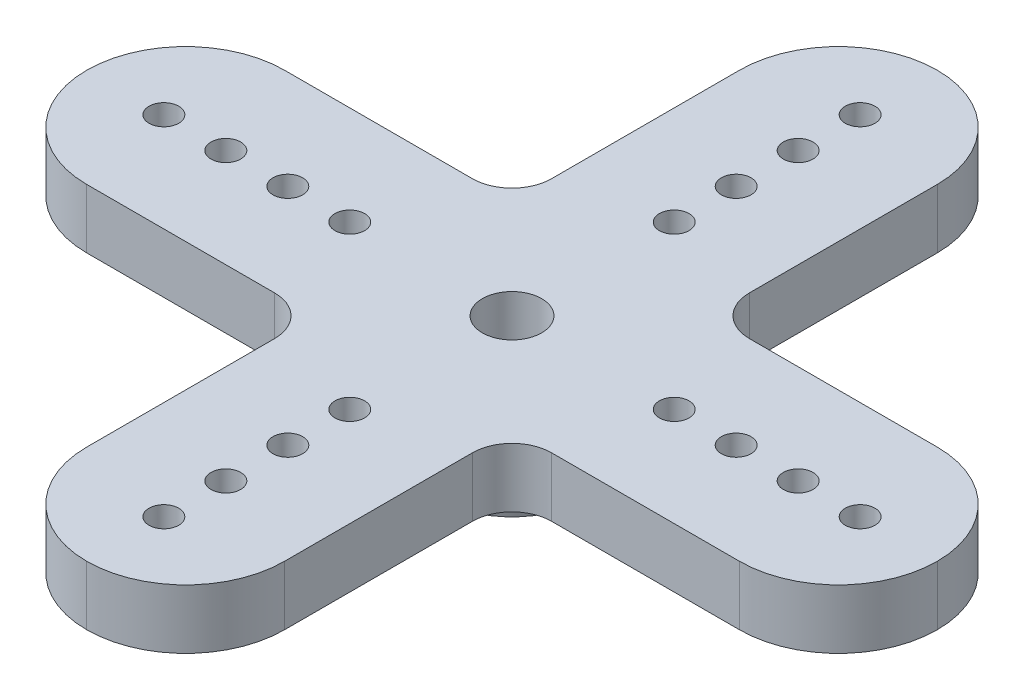
SolidWorks part; units mm, degrees
ref_plane "Front Plane" through (0, 0, 0) normal (0, 0, 1) x (1, 0, 0)
ref_plane "Top Plane" through (0, 0, 0) normal (0, 1, 0) x (1, 0, 0)
ref_plane "Right Plane" through (0, 0, 0) normal (1, 0, 0) x (0, 0, -1)
sketch "Sketch1" plane through (0, 0, 0) normal (0, 1, 0) x (1, 0, 0)
  line L0 (-5, 5) -> (-5, 21.5)
  line L1 (-5, 21.5) -> (5, 21.5)
  line L2 (5, 21.5) -> (5, 5)
  line L3 (5, 5) -> (21.5, 5)
  line L4 (21.5, 5) -> (21.5, -5)
  line L5 (21.5, -5) -> (5, -5)
  line L6 (5, -5) -> (5, -21.5)
  line L7 (5, -21.5) -> (-5, -21.5)
  line L8 (-5, -21.5) -> (-5, -5)
  line L9 (-5, -5) -> (-21.5, -5)
  line L10 (-21.5, -5) -> (-21.5, 5)
  line L11 (-21.5, 5) -> (-5, 5)
  point P2 (0, 21.5)
  point P13 (-21.5, 0)
  dimension "D1" = 10
  dimension "D2" = 43
extrude "Boss-Extrude1" add sketch "Sketch1" along normal blind 3
fillet "Fillet1" radius 2 4 edges at (-5, 1.5, -5) (5, 1.5, -5) (-5, 1.5, 5) (5, 1.5, 5)
fillet "Fillet2" radius 5 8 edges at (-21.5, 1.5, -5) (-5, 1.5, -21.5) (-21.5, 1.5, 5) (5, 1.5, -21.5) (21.5, 1.5, -5) (21.5, 1.5, 5) (5, 1.5, 21.5) (-5, 1.5, 21.5)
sketch "Sketch2" plane through (0, 0, 0) normal (0, -1, 0) x (1, 0, 0)
  circle A0 centre (0, 0) radius 4.5
  dimension "D1" = 9
extrude "Boss-Extrude2" add sketch "Sketch2" along normal blind 3
draft "Draft1" type of draft neutral plane draft angle 10 faces to draft 1 face at (0, -3, -4.5) neutral plane through (0, 0, 0) neutral plane normal (0, -1, 0) parameters "D1"=10
sketch "Sketch3" plane through (0, -3, 0) normal (0, -1, 0) x (1, 0, 0)
  circle A0 centre (0, 0) radius 3
  dimension "D1" = 6
extrude "Cut-Extrude1" cut sketch "Sketch3" against normal blind 3
sketch "Sketch4" plane through (0, 0, 0) normal (0, -1, 0) x (1, 0, 0)
  circle A0 centre (0, 0) radius 1.5
  dimension "D1" = 3
extrude "Cut-Extrude2" cut sketch "Sketch4" against normal through all
sketch "Sketch5" plane through (0, 3, 0) normal (0, 1, 0) x (1, 0, 0)
  line L0 (0, 0) -> (0, 21.5) construction
  line L1 (0, 8.2) -> (0, 11.3333) construction
  line L2 (0, 11.3333) -> (0, 14.4667) construction
  line L3 (0, 14.4667) -> (0, 17.6) construction
  arc A0 (5, 16.5) -> (0, 21.5) centre (0, 16.5) ccw construction
  circle A1 centre (0, 17.6) radius 0.75
  circle A2 centre (0, 14.4667) radius 0.75
  circle A3 centre (0, 11.3333) radius 0.75
  circle A4 centre (0, 8.2) radius 0.75
  dimension "D2" = 1.5
  dimension "D1" = 9.4
  dimension "D3" = 8.2
extrude "Cut-Extrude3" cut sketch "Sketch5" against normal through all
ref_axis "Axis1" through (0, 3, 0) along (0, -1, 0)
pattern_circular "CirPattern1" count 4 over 360 about axis through (0, 3, 0) along (0, -1, 0) of "Cut-Extrude3"
